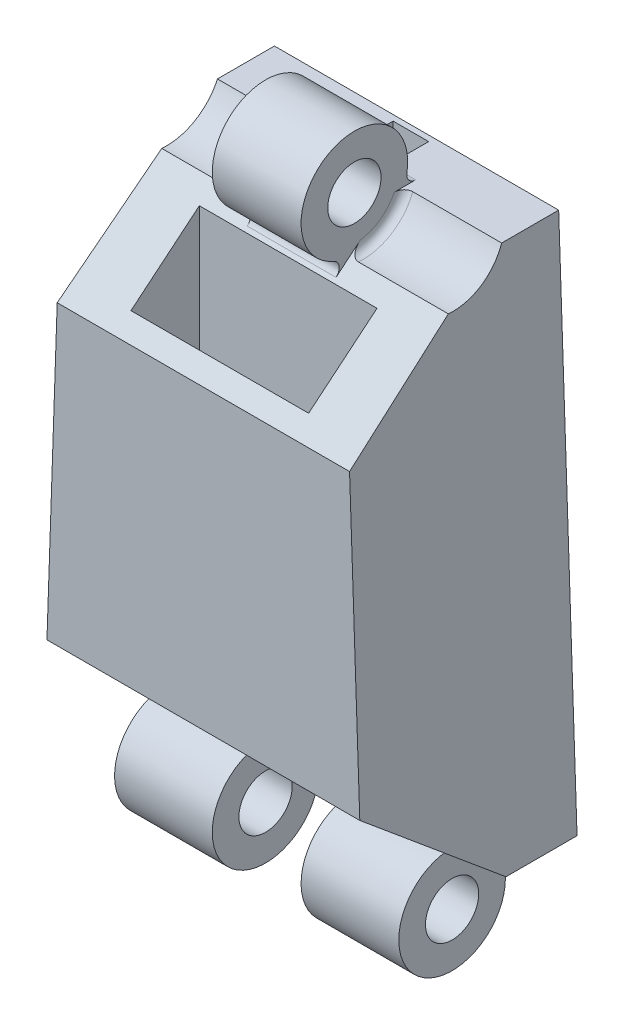
SolidWorks part; units mm, degrees
ref_plane "Front Plane" through (0, 0, 0) normal (0, 0, 1) x (1, 0, 0)
ref_plane "Top Plane" through (0, 0, 0) normal (0, 1, 0) x (1, 0, 0)
ref_plane "Right Plane" through (0, 0, 0) normal (1, 0, 0) x (0, 0, -1)
sketch "Sketch1" plane through (0, 0, 0) normal (0, 0, 1) x (1, 0, 0)
  line L0 (-8, -14.5) -> (-6.9661, 15.4822)
  line L3 (-8, -14.5) -> (10.0677, -14.5)
  line L5 (10.0677, -14.5) -> (9.0339, 15.4822)
  line L6 (-6.9661, 15.4822) -> (9.0339, 15.4822)
  point P0 (0, 0)
extrude "Boss-Extrude2" add sketch "Sketch1" along normal blind 12
sketch "Sketch15" plane through (0, 0, 0) normal (0, 0, -1) x (-1, 0, 0)
  line L0 (6.9661, 15.4822) -> (-9.0339, 15.4822)
  line L1 (-1.0339, 15.4822) -> (-1.0339, 5.488)
ref_plane "Plane1" through (1.0339, 0, 0) normal (1, 0, 0) x (0, 0, -1)
sketch "Sketch16" plane through (1.0339, 0, 0) normal (1, 0, 0) x (0, 0, -1)
  line L0 (0, 15.4822) -> (-4, 15.4822)
  line L6 (-12, 15.4822) -> (0, 15.4822) construction
  line L7 (-4, 15.4822) -> (-12, 8.8525)
  line L8 (-12, -14.5) -> (-12, 15.4822) construction
  line L9 (-12, 8.8525) -> (-12, 15.4822)
  line L10 (-12, 15.4822) -> (-4, 15.4822)
extrude "Cut-Extrude2" cut sketch "Sketch16" against normal through all both and the other way through all contours L10 L9 L7 region at (1.0339, 13.2723, 9.3333)
sketch "Sketch17" plane through (1.0339, 0, 0) normal (1, 0, 0) x (0, 0, -1)
  line L0 (-12, 8.8525) -> (-12, 18.723)
  line L1 (0, 15.4822) -> (-12, 15.4822)
  line L2 (-6, 15.4822) -> (-6, 16.5822)
  circle A0 centre (-6, 16.5822) radius 1.5
  circle A1 centre (-6, 16.5822) radius 3
extrude "Boss-Extrude3" add sketch "Sketch17" along normal mid plane 5 contours L1 A1 A0 | L1 A1 A0 region at (1.0339, 14.6478, 6) region at (1.0339, 15.5549, 4.0946)
sketch "Sketch18" plane through (1.0339, 0, 0) normal (1, 0, 0) x (0, 0, -1)
  line L0 (0, -14.5) -> (-4, -14.5)
  line L1 (-12, -14.5) -> (0, -14.5) construction
  line L2 (-4, -14.5) -> (-12, -7.8704)
  line L3 (-12, -14.5) -> (-12, 8.8525) construction
  line L4 (-12, -7.8704) -> (-12, -14.5)
  line L5 (-12, -14.5) -> (-4, -14.5)
extrude "Cut-Extrude3" cut sketch "Sketch18" against normal through all both and the other way through all contours L4 L5 L2 region at (1.0339, -12.2901, 9.3333)
sketch "Sketch19" plane through (1.0339, 0, 0) normal (1, 0, 0) x (0, 0, -1)
  line L0 (-12, -7.8704) -> (-12, -19.6668)
  line L1 (0, -14.5) -> (-3.2089, -14.5)
  line L3 (-8.7911, -14.5) -> (-12, -14.5)
  circle A0 centre (-6, -15.6) radius 1.5
  circle A1 centre (-6, -15.6) radius 3
extrude "Boss-Extrude4" add sketch "Sketch19" along normal mid plane 16 contours A1 A0 region at (1.0339, -18.4639, 6.544)
extrude "Cut-Extrude4" cut sketch "Sketch19<3>" against normal mid plane 5 contours A1
sketch "Sketch19<3>" plane through (1.0339, 0, 0) normal (1, 0, 0) x (0, 0, -1) same geometry as "Sketch19"
sketch "Sketch20" plane through (3.5339, 0, 0) normal (1, 0, 0) x (0, 0, -1)
  circle A0 centre (-6, 16.5822) radius 3
extrude "Cut-Extrude5" cut sketch "Sketch20" along normal blind 10
sketch "Sketch21" plane through (-1.4661, 0, 0) normal (-1, 0, 0) x (0, 0, 1)
  circle A0 centre (6, 16.5822) radius 3
extrude "Cut-Extrude6" cut sketch "Sketch21" along normal blind 10
fillet "Fillet6" radius 0.5 1 edges at (1.0339, 13.595, 6.2772)
fillet "Fillet7" radius 0.5 1 edges at (1.0339, 15.4822, 3.2089)
fillet "Fillet8" radius 0.5 2 edges at (3.5339, 14.0268, 4.4283) (-1.4661, 14.0268, 4.4283)
sketch "Sketch23" plane through (0, 11.1439, 9.235) normal (0, 0.77, 0.6381) x (1, 0, 0)
  line L0 (1.0339, -3.591) -> (1.0339, -2.391)
  line L1 (-7.1947, -3.591) -> (9.2625, -3.591) construction
  line L2 (1.0339, -6.6) -> (1.0339, 6.6) construction
  line L3 (9.1807, 0.1252) -> (7.9807, 0.1252)
  line L4 (9.2625, -3.591) -> (9.0989, 3.8414) construction
  line L5 (-3.9661, -2.391) -> (6.0339, -2.391)
  line L6 (6.0339, -2.391) -> (6.0339, 2.609)
  line L7 (6.0339, 2.609) -> (-3.9661, 2.609)
  line L8 (-3.9661, 2.609) -> (-3.9661, -2.391)
  point P13 (1.0339, -2.391)
  point P16 (7.9807, 0.1252)
sketch "Sketch24" plane through (0, 0, 0) normal (0, 1, 0) x (1, 0, 0)
  line L0 (-3.9661, -7.2262) -> (-3.9661, -11.076)
  line L1 (-3.9661, -11.076) -> (6.0339, -11.076)
  line L2 (6.0339, -11.076) -> (6.0339, -7.2262)
  line L3 (6.0339, -7.2262) -> (-3.9661, -7.2262)
extrude "Cut-Extrude7" cut sketch "Sketch24" along normal up to surface and the other way up to surface up to face at (1.0451, 12.5917, 7.4879) other way up to face at (1.0339, -12.4192, 6.5109)
sketch "Sketch25" plane through (1.0339, 0, 0) normal (1, 0, 0) x (0, 0, -1)
  line L4 (-4, -14.5) -> (0, -14.5) construction
  line L6 (-2.32, -14.5) -> (-0.32, -14.5)
  line L7 (-2.32, -14.5) -> (-2.32, 19.4904)
  line L8 (-2.32, 19.4904) -> (-0.32, 19.4904)
  line L9 (-0.32, -14.5) -> (-0.32, 19.4904)
extrude "Cut-Extrude8" cut sketch "Sketch25" against normal mid plane 2
